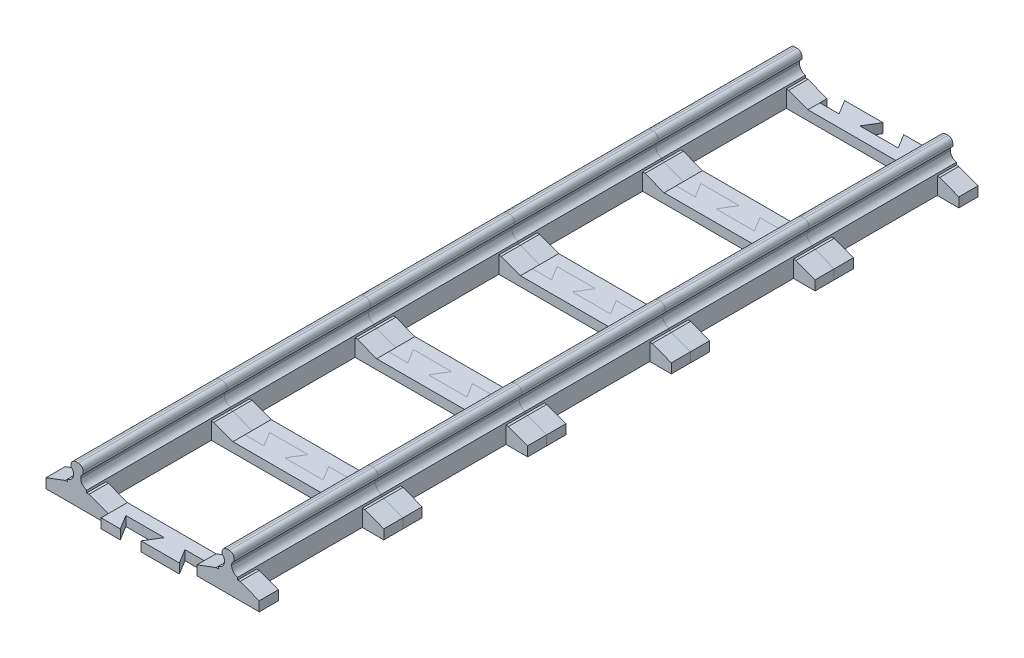
SolidWorks part; units mm, degrees
other "标注1"
sketch "草图3" plane through (-22.25, 4, -10) normal (-0.231, 0.6469, -0.7268) x (-0.9696, -0.2151, 0.1167)
other "标注2"
sketch "草图4" plane through (22.25, 8, -30) normal (0.0083, 0.0567, -0.9984) x (-0.9991, 0.0415, -0.0059)
ref_plane "前视基准面" through (0, 0, 0) normal (0, 0, 1) x (1, 0, 0)
ref_plane "上视基准面" through (0, 0, 0) normal (0, 1, 0) x (1, 0, 0)
ref_plane "右视基准面" through (0, 0, 0) normal (1, 0, 0) x (0, 0, -1)
other "Configuration Table"
sketch "草图1" plane through (0, 0, 0) normal (0, 1, 0) x (1, 0, 0)
  line L0 (-13.75, 9.5) -> (-13.75, -9.5)
  line L13 (-17.75, -9.5) -> (17.75, -9.5)
  line L21 (-17.75, -9.5) -> (-17.75, 9.5)
  line L22 (-17.75, 9.5) -> (17.75, 9.5)
  line L23 (17.75, -9.5) -> (17.75, 9.5)
  line L24 (-17.75, -9.5) -> (17.75, 9.5) construction
  line L25 (-17.75, 9.5) -> (17.75, -9.5) construction
  line L27 (13.75, 9.5) -> (13.75, -9.5)
  line L29 (-13.75, 0) -> (13.75, 0) construction
  line L32 (-22.25, 9.5) -> (22.25, 9.5)
  line L33 (-22.25, 9.5) -> (-22.25, 1.5)
  line L34 (-22.25, 1.5) -> (22.25, 1.5)
  line L35 (22.25, 9.5) -> (22.25, 1.5)
  point P0 (0, 0)
  point P15 (0, 1.5)
  dimension "D3" = 27.5
  dimension "D4" = 8
  dimension "D1" = 35.5
  dimension "D2" = 19
  dimension "D5" = 44.5
extrude "凸台-拉伸1" add sketch "草图1" along normal blind 4 contours L34 L21 L13 L0 | L34 L27 L13 L23 | L27 L34 L23 L22 | L21 L34 L0 L22 region at (-15.75, 0, -5.5) region at (-15.75, 0, 4) region at (15.75, 0, -5.5) region at (15.75, 0, 4)
extrude "凸台-拉伸2" add sketch "草图1<7>" along normal blind 3.5 contours L34 L35 L32 L33
sketch "草图1<7>" plane through (0, 0, 0) normal (0, 1, 0) x (1, 0, 0) same geometry as "草图1"
sketch "草图2" plane through (0, 0, -9.5) normal (0, 0, -1) x (-1, 0, 0)
  line L0 (18.25, 3.5) -> (22.25, 2)
  line L1 (22.25, 3.5) -> (18.25, 3.5)
  line L2 (22.25, 3.5) -> (22.25, 2)
  line L3 (22.25, 2) -> (18.25, 2) construction
  line L4 (18.25, 3.5) -> (18.25, 2) construction
  line L5 (-22.25, 2) -> (-18.25, 3.5)
  line L6 (-22.25, 3.5) -> (-18.25, 3.5)
  line L7 (-22.25, 3.5) -> (-22.25, 2)
  line L8 (-22.25, 2) -> (-18.25, 2) construction
  line L9 (-18.25, 3.5) -> (-18.25, 2) construction
  line L10 (13.75, 3.5) -> (-13.75, 3.5) construction
  line L11 (-13.25, 3.5) -> (-9.25, 3.5)
  line L12 (-13.25, 3.5) -> (-13.25, 2) construction
  line L13 (-13.25, 2) -> (-9.25, 2) construction
  line L14 (-9.25, 3.5) -> (-9.25, 2)
  line L15 (-13.75, 3.5) -> (-13.25, 3.5) construction
  line L16 (13.25, 3.5) -> (9.25, 3.5)
  line L17 (13.25, 3.5) -> (13.25, 2) construction
  line L18 (13.25, 2) -> (9.25, 2) construction
  line L19 (9.25, 3.5) -> (9.25, 2)
  line L20 (13.25, 3.5) -> (13.75, 3.5) construction
  line L21 (17.75, 3.5) -> (18.25, 3.5) construction
  line L22 (-13.25, 3.5) -> (-9.25, 2)
  line L23 (9.25, 2) -> (13.25, 3.5)
  line L24 (-9.25, 2) -> (9.25, 2)
  line L25 (-9.25, 3.5) -> (9.25, 3.5)
  line L26 (-15.75, 4) -> (-15.75, 6.5) construction
  line L27 (14.5, 8) -> (17, 8)
  line L28 (14.5, 8) -> (14.5, 6.5)
  line L29 (14.5, 6.5) -> (17, 6.5)
  line L30 (17, 8) -> (17, 6.5)
  line L31 (-17, 8) -> (-14.5, 8)
  line L32 (-17, 8) -> (-17, 6.5)
  line L33 (-17, 6.5) -> (-14.5, 6.5)
  line L34 (-14.5, 8) -> (-14.5, 6.5)
  line L35 (-13.75, 4) -> (-17.75, 4) construction
  line L36 (15.75, 6.5) -> (15.75, 4) construction
  line L37 (17.75, 4) -> (13.75, 4) construction
  line L38 (15, 6.5) -> (15, 4)
  line L39 (16.5, 6.5) -> (16.5, 4)
  line L40 (16.5, 4) -> (15.75, 4)
  line L41 (15.75, 4) -> (15, 4)
  line L42 (-16.5, 6.5) -> (-16.5, 4)
  line L43 (-16.5, 4) -> (-15.75, 4)
  line L44 (-15.75, 4) -> (-15, 4)
  line L45 (-15, 4) -> (-15, 6.5)
  line M9 (22.25, 3.5) -> (17.75, 3.5)
  line M11 (17.75, 4) -> (13.75, 4)
  line M13 (13.75, 3.5) -> (-13.75, 3.5)
  line M15 (-13.75, 4) -> (-17.75, 4)
  line M17 (-17.75, 3.5) -> (-22.25, 3.5)
  line M18 (-22.25, 3.5) -> (-22.25, 0)
  line M20 (22.25, 0) -> (22.25, 3.5)
  dimension "D1" = 4
  dimension "D2" = 1.5
  dimension "D3" = 2.5
  dimension "D4" = 1.5
  dimension "D5" = 2.5
  dimension "D6" = 1.5
extrude "切除-拉伸1" cut sketch "草图2" against normal through all contours L14 L24 L19 M13 | L19 L23 M13 | L22 L14 M13 | L5 M18 M17 | L0 M9 M20 region at (-20.9167, 3, -9.5) region at (20.9167, 3, -9.5) region at (10.5833, 3, -9.5) region at (0, 2.75, -9.5) region at (-10.5833, 3, -9.5)
extrude "凸台-拉伸4" add sketch "草图2<3>" against normal through all contours L34 L31 L32 L33 | L45 L33 L42 M15 | L30 L27 L28 L29 | L39 L29 L38 M11 region at (-15.75, 7.25, -9.5) region at (-15.75, 5.25, -9.5) region at (15.75, 7.25, -9.5) region at (15.75, 5.25, -9.5)
sketch "草图2<3>" plane through (0, 0, -9.5) normal (0, 0, -1) x (-1, 0, 0) same geometry as "草图2"
fillet "圆角1" radius 1 4 edges at (-16.5, 6.5, 0) (-15, 6.5, 0) (15, 6.5, 0) (16.5, 6.5, 0)
fillet "圆角2" radius 1.5 4 edges at (16.5, 4, 0) (15, 4, 0) (-15, 4, 0) (-16.5, 4, 0)
fillet "圆角3" radius 1 4 edges at (-17, 8, 0) (14.5, 8, 0) (17, 8, 0) (-14.5, 8, 0)
sketch "草图8" plane through (22.25, 0, 0) normal (1, 0, 0) x (0, 0, -1)
  line L0 (5.5, 0) -> (5.5, 18.5305)
  line L1 (9.5, 0) -> (1.5, 0) construction
mirror "镜向2" about plane through (0, 4, 9.5) normal (0, 0, -1) of bodies 192
sketch "草图9" plane through (0, 2, 0) normal (0, 1, 0) x (1, 0, 0)
  line L0 (-22.25, 5.5) -> (-9.25, 5.5)
  line L1 (-22.25, 1.5) -> (-22.25, 9.5) construction
  line L2 (-9.25, 1.5) -> (-9.25, 9.5) construction
  line L3 (-9.25, 5.5) -> (-9.25, 4)
  line L4 (-9.25, 4) -> (-5.25, 4)
  line L5 (-5.25, 4) -> (-7.0833, 7)
  line L6 (-7.0833, 7) -> (0.9167, 7)
  line L7 (0.9167, 7) -> (-0.9167, 4)
  line L8 (-0.9167, 4) -> (7.0833, 4)
  line L9 (7.0833, 4) -> (5.25, 7)
  line L10 (9.25, 1.5) -> (9.25, 9.5) construction
  line L11 (9.25, 5.5) -> (22.25, 5.5)
  line L12 (5.25, 7) -> (9.25, 7)
  line L13 (-22.25, 5.5) -> (-22.25, 9.5)
  line L14 (9.25, 7) -> (9.25, 5.5)
  line L15 (-22.25, 9.5) -> (22.25, 9.5)
  line L16 (22.25, 9.5) -> (22.25, 5.5)
  line L17 (22.25, 1.5) -> (22.25, 9.5) construction
  line L18 (-22.25, -24.5) -> (-9.25, -24.5)
  line L19 (-22.25, -20.5) -> (-22.25, -28.5) construction
  line L20 (-9.25, -20.5) -> (-9.25, -28.5) construction
  line L21 (-9.25, -24.5) -> (-9.25, -26)
  line L22 (-9.25, -26) -> (-5.25, -26)
  line L23 (-5.25, -26) -> (-7.0833, -23)
  line L24 (-7.0833, -23) -> (0.9167, -23)
  line L25 (0.9167, -23) -> (-0.9167, -26)
  line L26 (-0.9167, -26) -> (7.0833, -26)
  line L27 (7.0833, -26) -> (5.25, -23)
  line L28 (5.25, -23) -> (9.25, -23)
  line L29 (9.25, -20.5) -> (9.25, -28.5) construction
  line L30 (9.25, -23) -> (9.25, -24.5)
  line L31 (9.25, -24.5) -> (22.25, -24.5)
  line L32 (22.25, -20.5) -> (22.25, -28.5) construction
  line L33 (22.25, -24.5) -> (22.25, -28.5)
  line L34 (22.25, -28.5) -> (-22.25, -28.5)
  line L35 (-22.25, -28.5) -> (-22.25, -24.5)
  dimension "D1" = 3
  dimension "D2" = 8
  dimension "D3" = 4
extrude "切除-拉伸2" cut sketch "草图9" against normal through all both and the other way through all
pattern_linear "阵列(线性)1" count 5 spacing 30 along (0, 0, -1) of bodies 203
